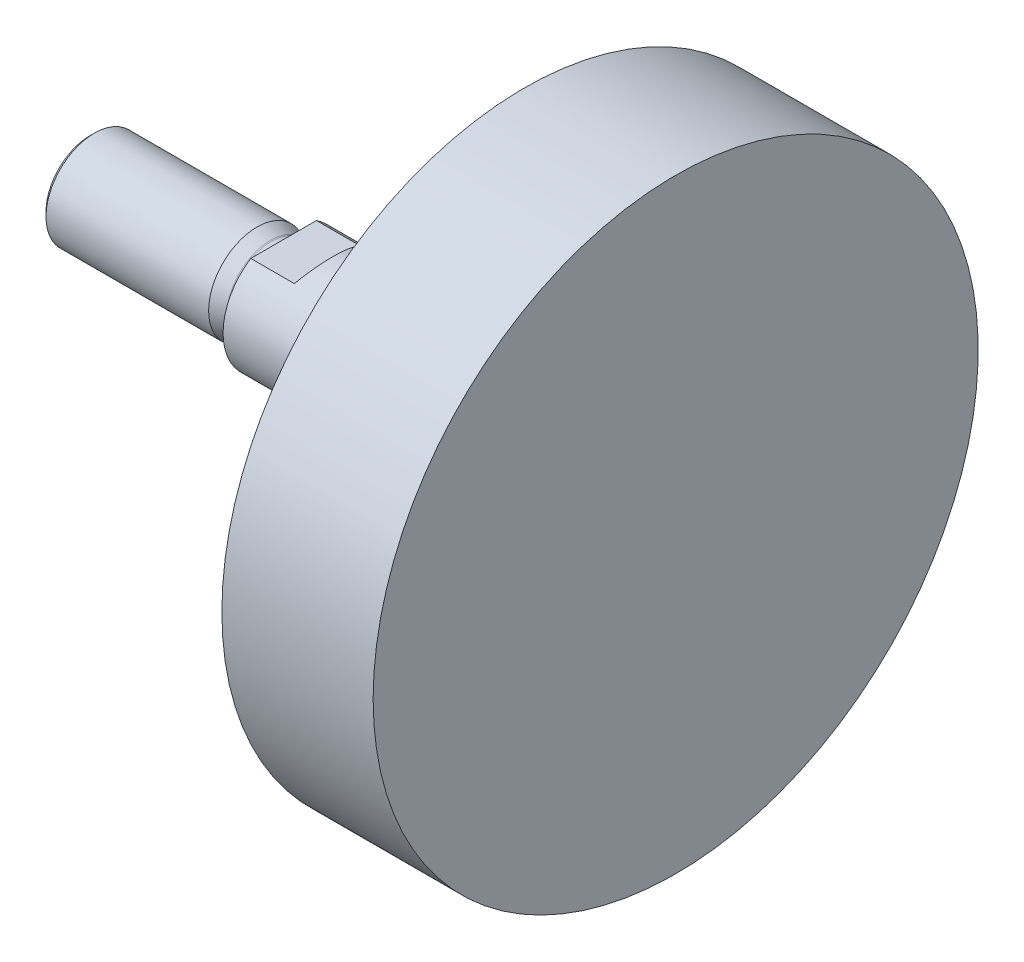
SolidWorks part; units mm, degrees
ref_plane "Front Plane" through (0, 0, 0) normal (0, 0, 1) x (1, 0, 0)
ref_plane "Top Plane" through (0, 0, 0) normal (0, 1, 0) x (1, 0, 0)
ref_plane "Right Plane" through (0, 0, 0) normal (1, 0, 0) x (0, 0, -1)
sketch "Sketch1" plane through (0, 0, 0) normal (0, 0, 1) x (1, 0, 0)
  line L0 (-11, 0) -> (-11, 12.5)
  line L1 (-11, 12.5) -> (70, 12.5)
  line L2 (70, 12.5) -> (70, 0)
  line L3 (70, 0) -> (-11, 0)
  line L4 (70, 0) -> (-11, 0) construction
revolve "Revolve1" add sketch "Sketch1" angle 360 about L4 reverse direction yes
sketch "Sketch2" plane through (0, 0, 0) normal (0, 0, 1) x (1, 0, 0)
  line L0 (38.75, 0) -> (38.75, 62.5)
  line L1 (38.75, 62.5) -> (70, 62.5)
  line L2 (70, 62.5) -> (70, 0)
  line L3 (70, 0) -> (38.75, 0)
  line L4 (70, 0) -> (38.75, 0) construction
revolve "Revolve2" add sketch "Sketch2" angle 360 about L4 reverse direction yes
ref_plane "Plane1" through (-11, 0, 0) normal (1, 0, 0) x (0, 0, -1)
sketch "Sketch3" plane through (0, 0, 0) normal (0, 0, 1) x (1, 0, 0)
  line L0 (-51, 0) -> (-51, 9.08)
  line L1 (-51, 9.08) -> (-50.08, 10)
  line L2 (-50.08, 10) -> (-16.4849, 10)
  line L3 (-16.4849, 10) -> (-13.7243, 8.9952)
  line L4 (-13.4678, 8.95) -> (-11.75, 8.95)
  line L5 (-11, 9.7) -> (-11, 10)
  line L6 (-11, 10) -> (-10, 10)
  line L7 (-10, 10) -> (-10, 0)
  line L8 (-10, 0) -> (-51, 0)
  line L9 (-10, 0) -> (-51, 0) construction
  arc A0 (-13.7243, 8.9952) -> (-13.4678, 8.95) centre (-13.4678, 9.7) ccw
  arc A1 (-11.75, 8.95) -> (-11, 9.7) centre (-11.75, 9.7) ccw
revolve "Revolve3" add sketch "Sketch3" angle 360 about L9 reverse direction yes
cosmetic thread "Cosmetic Thread1" parameters "D1"=37.0428, "D2"=18.16
sketch "Sketch4" plane through (0, 0, 0) normal (0, 0, 1) x (1, 0, 0)
  line L0 (-67, -28) -> (8.1036, -28)
  line L1 (8.1036, -28) -> (-2, -10.5)
  line L2 (-2, -10.5) -> (-11, -10.5)
  line L3 (-11, -10.5) -> (-11, -15.5)
  line L4 (-11, -15.5) -> (-56, -15.5)
  line L5 (-56, -15.5) -> (-56, 15.5)
  line L6 (-56, 15.5) -> (-11, 15.5)
  line L7 (-11, 15.5) -> (-11, 10.5)
  line L8 (-11, 10.5) -> (-2, 10.5)
  line L9 (-2, 10.5) -> (8.1036, 28)
  line L10 (8.1036, 28) -> (-67, 28)
  line L11 (-67, 28) -> (-67, -28)
extrude "Cut-Extrude1" cut sketch "Sketch4" along normal blind 25 and the other way blind 25
ref_plane "Plane2" through (70, 0, 0) normal (1, 0, 0) x (0, 0, -1)
ref_plane "Plane3" through (-23, 0, 0) normal (1, 0, 0) x (0, 0, -1)
ref_plane "Plane4" through (-28, 0, 0) normal (1, 0, 0) x (0, 0, -1)
ref_plane "Plane5" through (0, 0, 0) normal (0, 0, 1) x (1, 0, 0)
ref_plane "Plane6" through (0, 0, 0) normal (0, 0, 1) x (1, 0, 0)
ref_plane "FDT_PIRODACC_M1 XY" through (-28, 0, 0) normal (-1, 0, 0) x (0, 0, 1)
ref_plane "FDT_PIRODACC_M1 XZ" through (0, 0, 0) normal (0, 0, 1) x (1, 0, 0)
ref_plane "FDT_PIRODACC_M1 YZ" through (0, 0, 0) normal (0, 1, 0) x (1, 0, 0)
ref_axis "FDT_PIRODACC_M1 X" through (-28, -50, 0) along (0, 1, 0)
ref_axis "FDT_PIRODACC_M1 Y" through (-28, 0, 80.9) along (0, 0, -1)
ref_axis "FDT_PIRODACC_M1 Z" through (-80.9, 0, 0) along (1, 0, 0)
sketch3d "FDT_PIRODACC_M1"
  point P0 (-28, 0, 0)
ref_plane "NUT1 XY" through (-23, 0, 0) normal (1, 0, 0) x (0, 0, -1)
ref_plane "NUT1 XZ" through (0, 0, 0) normal (0, -1, 0) x (-1, 0, 0)
ref_plane "NUT1 YZ" through (0, 0, 0) normal (0, 0, -1) x (-1, 0, 0)
ref_axis "NUT1 X" through (-23, 0, 80.9) along (0, 0, -1)
ref_axis "NUT1 Y" through (-23, -50, 0) along (0, 1, 0)
ref_axis "NUT1 Z" through (80.9, 0, 0) along (-1, 0, 0)
sketch3d "NUT1"
  point P0 (-23, 0, 0)
ref_plane "PISTON XY" through (70, 0, 0) normal (1, 0, 0) x (0, 0, -1)
ref_plane "PISTON XZ" through (0, 0, 0) normal (0, -1, 0) x (-1, 0, 0)
ref_plane "PISTON YZ" through (0, 0, 0) normal (0, 0, -1) x (-1, 0, 0)
ref_axis "PISTON X" through (70, 0, 80.9) along (0, 0, -1)
ref_axis "PISTON Y" through (70, -50, 0) along (0, 1, 0)
ref_axis "PISTON Z" through (80.9, 0, 0) along (-1, 0, 0)
sketch3d "PISTON"
  point P0 (70, 0, 0)
other "Freeze***"
